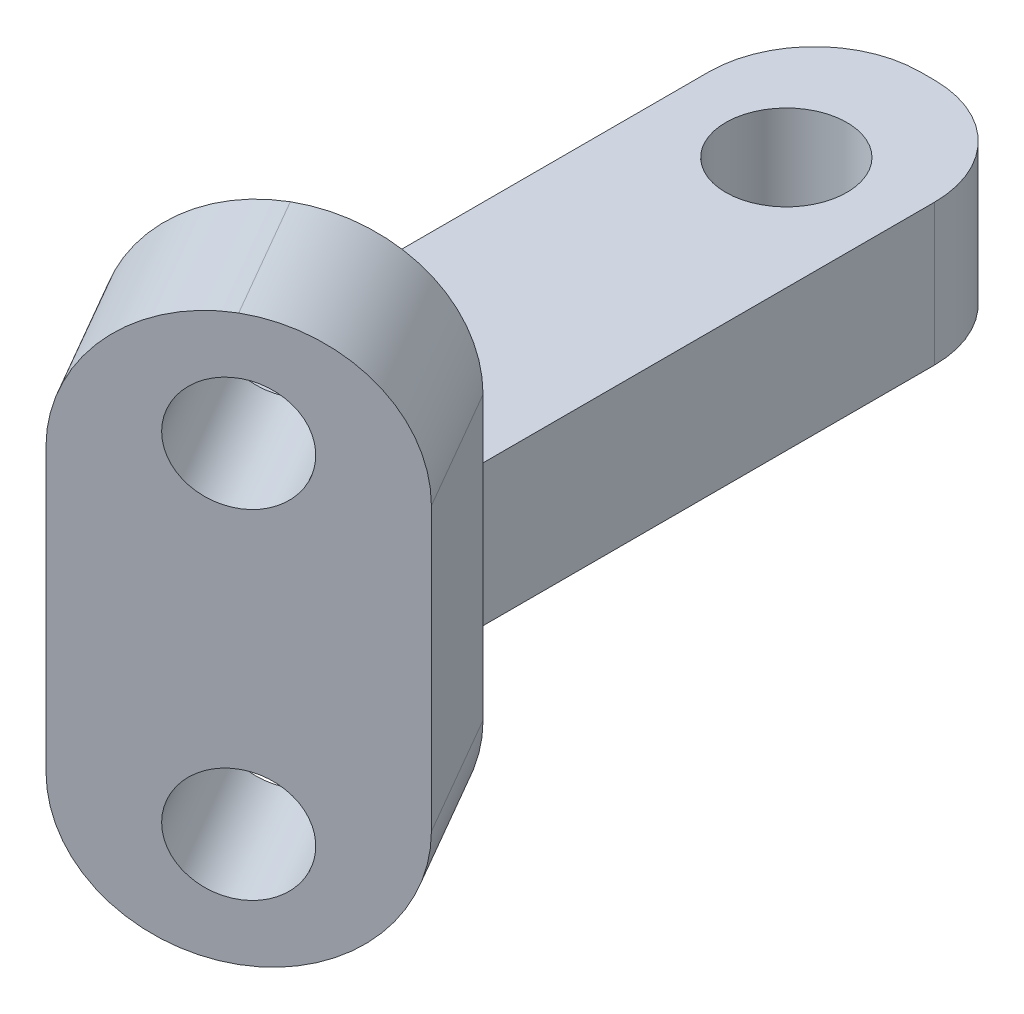
SolidWorks part; units mm, degrees
ref_plane "Front Plane" through (0, 0, 0) normal (0, 0, 1) x (1, 0, 0)
ref_plane "Top Plane" through (0, 0, 0) normal (0, 1, 0) x (1, 0, 0)
ref_plane "Right Plane" through (0, 0, 0) normal (1, 0, 0) x (0, 0, -1)
sketch "Sketch1" plane through (0, 0, 0) normal (0, 1, 0) x (1, 0, 0)
  line L0 (-4, -20) -> (4, -15.3812)
  line L2 (4, -5) -> (4, 1.25)
  line L3 (0.25, 5) -> (-0.25, 5)
  line L4 (-4, -5) -> (-4, 1.25)
  line L5 (4, -5) -> (-4, 5) construction
  line L6 (4, 5) -> (-4, -5) construction
  line L8 (-4, -5) -> (-4, -20)
  line L10 (4, -5) -> (4, -15.3812)
  circle A0 centre (0, 0) radius 2.1477
  arc A1 (4, 1.25) -> (0.25, 5) centre (0.25, 1.25) ccw
  arc A2 (-0.25, 5) -> (-4, 1.25) centre (-0.25, 1.25) ccw
  dimension "D1" = 8
  dimension "D3" = 3.75
  dimension "D2" = 10
  dimension "D4" = 15
extrude "Boss-Extrude1" add sketch "Sketch1" along normal blind 5
sketch "Sketch2" plane through (7.6603, 0, 13.2679) normal (0.5, 0, 0.866) x (0.866, 0, -0.5)
  line L0 (-4.2265, 5) -> (-4.2265, 0) construction
  line L1 (-3.7641, 12.5) -> (-13.7641, 12.5)
  line L2 (-3.7641, 12.5) -> (-3.7641, -7.5)
  line L3 (-3.7641, -7.5) -> (-13.7641, -7.5)
  line L4 (-13.7641, 12.5) -> (-13.7641, -7.5)
  line L5 (-13.4641, 5) -> (-13.4641, 0) construction
  line L6 (-13.4641, 5) -> (-4.2265, 5) construction
  dimension "D1" = 10
  dimension "D2" = 20
  dimension "D3" = 0.3
  dimension "D4" = 7.5
extrude "Boss-Extrude2" add sketch "Sketch2" along normal blind 5
sketch "Sketch3" plane through (7.6603, 0, 13.2679) normal (-0.5, 0, -0.866) x (-0.866, 0, 0.5)
  line L0 (8.7641, -7.5) -> (8.7641, 12.5) construction
  line L1 (13.7641, -7.5) -> (3.7641, -7.5) construction
  line L2 (3.7641, 12.5) -> (13.7641, 12.5) construction
  circle A0 centre (8.7641, -3.5) radius 2
  circle A1 centre (8.7641, 8.5) radius 2
  dimension "D1" = 4
  dimension "D2" = 4
extrude "Cut-Extrude1" cut sketch "Sketch3" against normal blind 5
fillet "Fillet1" radius 5 4 edges at (5.6504, 12.5, 17.3151) (-3.0098, 12.5, 22.3151) (5.6504, -7.5, 17.3151) (-3.0098, -7.5, 22.3151)
